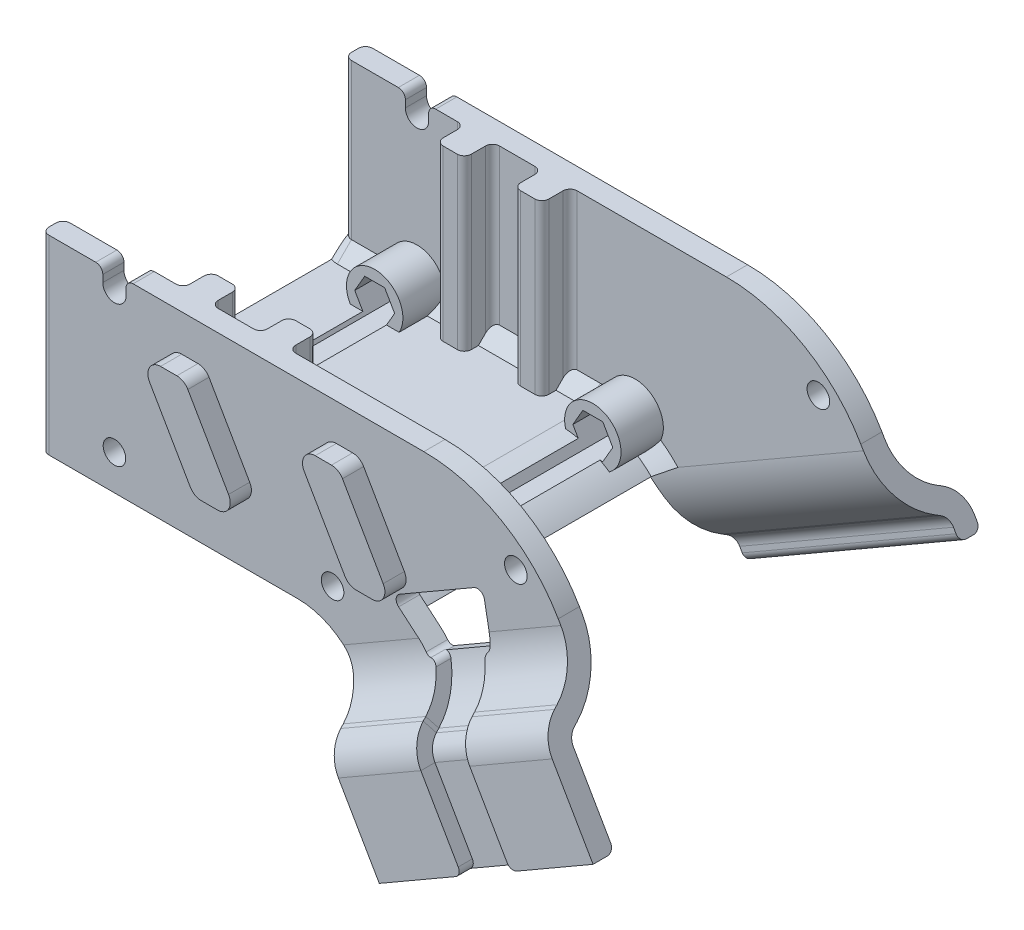
SolidWorks part; units mm, degrees
ref_plane "Front Plane" through (0, 0, 0) normal (0, 0, 1) x (1, 0, 0)
ref_plane "Top Plane" through (0, 0, 0) normal (0, 1, 0) x (1, 0, 0)
ref_plane "Right Plane" through (0, 0, 0) normal (1, 0, 0) x (0, 0, -1)
other "Configuration Table"
sketch "草图1" plane through (0, 145.9, 0) normal (0, 1, 0) x (1, 0, 0)
  line L14 (6.9526, -119.8723) -> (-44.7898, -119.8723) construction
  line L15 (-44.7898, -119.8723) -> (-47.2117, -119.8723) construction
  line L16 (6.9526, -73.9723) -> (-44.7898, -73.9723) construction
  line L17 (-47.2117, -73.9723) -> (-44.7898, -73.9723) construction
  line L18 (3.5151, -119.8723) -> (-44.7898, -119.8723)
  line L19 (-44.7898, -119.8723) -> (-47.2117, -119.8723)
  line L20 (3.5151, -73.9723) -> (-44.7898, -73.9723)
  line L21 (-47.2117, -73.9723) -> (-44.7898, -73.9723)
  line L22 (-47.2117, -73.9723) -> (-47.2117, -119.8723)
  line L23 (3.5151, -73.9723) -> (3.5151, -119.8723)
extrude "凸台-拉伸1" add sketch "草图1" against normal up to surface (30 mm away)
sketch "草图2" plane through (0, 0, 119.8723) normal (0, 0, 1) x (1, 0, 0)
  line L0 (3.5151, 145.9) -> (6.9526, 145.9)
  line L1 (-10.9453, 145.9) -> (-10.9453, 115.9)
  line L2 (-47.2117, 145.9) -> (3.5151, 145.9) construction
  line L3 (3.5151, 145.9) -> (-10.9453, 145.9)
  line L5 (28.9707, 132.7635) -> (-4.4253, 113.4822)
  line L6 (28.6032, 133.4) -> (28.9707, 132.7635)
  arc A0 (28.6032, 133.4) -> (6.9526, 145.9) centre (6.9526, 120.9) ccw construction
  arc A1 (28.6032, 133.4) -> (6.9526, 145.9) centre (6.9526, 120.9) ccw
  arc A2 (-4.4253, 113.4822) -> (-10.9453, 115.9) centre (-10.9453, 105.9) ccw construction
  arc A3 (-4.4253, 113.4822) -> (-10.9453, 115.9) centre (-10.9453, 105.9) ccw
extrude "凸台-拉伸5" add sketch "草图2" against normal up to surface (45.9 mm away) up to face at (-21.8483, 130.9, 73.9723)
sketch "草图4" plane through (0, 0, 119.8723) normal (0, 0, 1) x (1, 0, 0)
  line L0 (-4.4253, 113.4822) -> (6.9276, 120.0369)
  line L1 (3.5151, 118.0667) -> (28.9707, 132.7635) construction
  line L2 (6.9276, 120.0369) -> (8.6364, 117.0772)
  line L3 (8.6364, 117.0772) -> (-3.6007, 110.0121)
  line L4 (-3.6007, 110.0121) -> (-4.4253, 113.4822)
extrude "切除-拉伸1" cut sketch "草图4" against normal blind 72.5
shell "抽壳2" thickness 3
sketch "草图5" plane through (-50.2456, 87.0279, 0) normal (0.5, -0.866, 0) x (0.866, 0.5, 0)
  line L0 (91.4711, 73.9723) -> (91.4711, 119.8723) construction
  line L1 (52.9087, 119.8723) -> (91.4711, 119.8723)
  line L2 (52.9087, 119.8723) -> (52.9087, 116.8723)
  line L3 (52.9087, 116.8723) -> (91.4711, 116.8723)
  line L4 (91.4711, 119.8723) -> (91.4711, 116.8723)
  line L5 (56.0436, 116.8723) -> (88.4711, 116.8723) construction
sketch3d "3D草图1"
  line L0 (50.5425, 95.4, 126.8723) -> (34.7442, 122.7635, 126.8723) construction
  line L1 (50.5425, 95.4, 126.8723) -> (34.7442, 122.7635, 126.8723)
  line L2 (32.5792, 126.5135, 124.3723) -> (32.4348, 126.7635, 123.8723) construction
  line L5 (32.5792, 126.5135, 124.3723) -> (32.4348, 126.7635, 123.8723)
  arc A0 (32.5792, 126.5135, 124.3723) -> (34.7442, 122.7635, 126.8723) centre (34.7442, 122.7635, 121.8723) ccw construction
  arc A1 (28.9707, 132.7635, 119.8723) -> (32.4348, 126.7635, 123.8723) centre (28.9707, 132.7635, 127.8723) ccw construction
  arc A2 (32.5792, 126.5135, 124.3723) -> (34.7442, 122.7635, 126.8723) centre (34.7442, 122.7635, 121.8723) ccw
  arc A3 (28.9707, 132.7635, 119.8723) -> (32.4348, 126.7635, 123.8723) centre (28.9707, 132.7635, 127.8723) ccw
  point P5 (39.0743, 125.2635, 121.8723)
  point P8 (22.0425, 128.7635, 127.8723)
  point P9 (39.0743, 125.2635, 121.8723)
  point P10 (22.0425, 128.7635, 127.8723)
sweep "扫描2" add profiles "草图5" path "3D草图1"
ref_plane "基准面1" through (0, 0, 96.9223) normal (0, 0, -1) x (-1, 0, 0)
mirror "镜向1" about plane through (0, 0, 96.9223) normal (0, 0, -1) of "扫描2"
sketch "草图7" plane through (0, 0, 126.8723) normal (0, 0, 1) x (1, 0, 0)
  line L0 (40.5425, 112.7205) -> (7.1465, 93.4393)
  line L3 (7.1465, 93.4393) -> (17.1465, 76.1188)
  line L4 (17.1465, 76.1188) -> (50.5425, 95.4)
  line L5 (50.5425, 95.4) -> (40.5425, 112.7205)
  dimension "D1" = 20
extrude "切除-拉伸2" cut sketch "草图7" against normal blind 72.5
sketch "草图8" plane through (79.2163, 45.7356, 0) normal (0.866, 0.5, 0) x (0, 0, -1)
  line L0 (-66.9723, 88.9442) -> (-66.9723, 77.3476) construction
  line L1 (-69.9723, 93.563) -> (-69.4723, 93.2743) construction
  line L2 (-73.9723, 100.4912) -> (-73.9723, 101.2262) construction
  line L3 (-73.9723, 101.2262) -> (-119.8723, 101.2262) construction
  line L4 (-119.8723, 100.4912) -> (-119.8723, 101.2262) construction
  line L5 (-123.8723, 93.563) -> (-124.3723, 93.2743) construction
  line L6 (-126.8723, 88.9442) -> (-126.8723, 77.3476) construction
  line L7 (-66.9723, 88.9442) -> (-66.9723, 87.2262)
  line L8 (-69.9723, 93.563) -> (-69.4723, 93.2743)
  line L9 (-73.9723, 100.4912) -> (-73.9723, 101.2262)
  line L10 (-73.9723, 101.2262) -> (-119.8723, 101.2262)
  line L11 (-119.8723, 100.4912) -> (-119.8723, 101.2262)
  line L12 (-123.8723, 93.563) -> (-124.3723, 93.2743)
  line L13 (-126.8723, 88.9442) -> (-126.8723, 87.2262)
  line L15 (-126.8723, 87.2262) -> (-66.9723, 87.2262)
  arc A0 (-66.9723, 88.9442) -> (-69.4723, 93.2743) centre (-71.9723, 88.9442) ccw construction
  arc A1 (-73.9723, 100.4912) -> (-69.9723, 93.563) centre (-65.9723, 100.4912) ccw construction
  arc A2 (-123.8723, 93.563) -> (-119.8723, 100.4912) centre (-127.8723, 100.4912) ccw construction
  arc A3 (-124.3723, 93.2743) -> (-126.8723, 88.9442) centre (-121.8723, 88.9442) ccw construction
  arc A4 (-66.9723, 88.9442) -> (-69.4723, 93.2743) centre (-71.9723, 88.9442) ccw
  arc A5 (-73.9723, 100.4912) -> (-69.9723, 93.563) centre (-65.9723, 100.4912) ccw
  arc A6 (-123.8723, 93.563) -> (-119.8723, 100.4912) centre (-127.8723, 100.4912) ccw
  arc A7 (-124.3723, 93.2743) -> (-126.8723, 88.9442) centre (-121.8723, 88.9442) ccw
  dimension "D1" = 14
extrude "凸台-拉伸6" add sketch "草图8" against normal blind 3
sketch "草图9" plane through (0, 0, 66.9723) normal (0, 0, -1) x (-1, 0, 0)
  line L0 (-35.6032, 121.2756) -> (-2.2072, 101.9944)
  line L1 (-34.7442, 122.7635) -> (-40.5425, 112.7205) construction
  line L2 (-1.3482, 103.4822) -> (-7.1465, 93.4393) construction
  line L3 (-7.1465, 93.4393) -> (-40.5425, 112.7205) construction
  line L4 (-35.6032, 121.2756) -> (-40.5425, 112.7205)
  line L5 (-40.5425, 112.7205) -> (-7.1465, 93.4393)
  line L6 (-7.1465, 93.4393) -> (-2.2072, 101.9944)
extrude "切除-拉伸3" cut sketch "草图9" against normal blind 3
sketch "草图11" plane through (0, 0, 73.9723) normal (0, 0, -1) x (-1, 0, 0)
  line L0 (1.7732, 110.0135) -> (2.285, 110.9) construction
  line L1 (-1.8353, 103.7635) -> (1.6288, 109.7635) construction
  line L2 (-1.8353, 103.7635) -> (-17.6336, 76.4) construction
  line L3 (1.7732, 110.0135) -> (2.285, 110.9)
  line L4 (-1.8353, 103.7635) -> (1.6288, 109.7635)
  line L5 (-1.8353, 103.7635) -> (-17.6336, 76.4)
  line L7 (1.7732, 110.0135) -> (1.6288, 109.7635)
  line L8 (4.4253, 113.4822) -> (4.4253, 76.4)
  line L9 (4.4253, 76.4) -> (-17.6336, 76.4)
  arc A0 (10.9453, 115.9) -> (4.4253, 113.4822) centre (10.9453, 105.9) ccw construction
  arc A1 (4.4253, 113.4822) -> (2.285, 110.9) centre (10.9453, 105.9) ccw construction
  arc A2 (10.9453, 115.9) -> (4.4253, 113.4822) centre (10.9453, 105.9) ccw
  arc A3 (4.4253, 113.4822) -> (2.285, 110.9) centre (10.9453, 105.9) ccw
extrude "切除-拉伸4" cut sketch "草图11" against normal blind 68 and the other way blind 50 contours L8 A3 L3 L7 L4 L5 L9
sketch "草图12" plane through (0, 0, 73.9723) normal (0, 0, -1) x (-1, 0, 0)
  line L25 (19.2998, 124.1) -> (21.6092, 124.1)
  line L26 (23.1681, 125) -> (28.9416, 135)
  line L27 (27.3827, 137.7) -> (25.0733, 137.7)
  line L28 (23.5145, 136.8) -> (17.741, 126.8)
  line L29 (19.2998, 124.1) -> (21.6092, 124.1)
  line L30 (23.1681, 125) -> (28.9416, 135)
  line L31 (27.3827, 137.7) -> (25.0733, 137.7)
  line L32 (23.5145, 136.8) -> (17.741, 126.8)
  line L58 (-2.6284, 124.1) -> (-0.319, 124.1)
  line L59 (1.2399, 125) -> (7.0134, 135)
  line L60 (1.5863, 136.8) -> (-4.1872, 126.8)
  line L61 (5.4545, 137.7) -> (3.1451, 137.7)
  line L62 (-2.6284, 124.1) -> (-0.319, 124.1)
  line L63 (1.2399, 125) -> (7.0134, 135)
  line L64 (1.5863, 136.8) -> (-4.1872, 126.8)
  line L65 (5.4545, 137.7) -> (3.1451, 137.7)
  arc A20 (17.741, 126.8) -> (19.2998, 124.1) centre (19.2998, 125.9) ccw
  arc A21 (21.6092, 124.1) -> (23.1681, 125) centre (21.6092, 125.9) ccw
  arc A22 (28.9416, 135) -> (27.3827, 137.7) centre (27.3827, 135.9) ccw
  arc A23 (25.0733, 137.7) -> (23.5145, 136.8) centre (25.0733, 135.9) ccw
  arc A24 (17.741, 126.8) -> (19.2998, 124.1) centre (19.2998, 125.9) ccw
  arc A25 (21.6092, 124.1) -> (23.1681, 125) centre (21.6092, 125.9) ccw
  arc A26 (28.9416, 135) -> (27.3827, 137.7) centre (27.3827, 135.9) ccw
  arc A27 (25.0733, 137.7) -> (23.5145, 136.8) centre (25.0733, 135.9) ccw
  arc A47 (-4.1872, 126.8) -> (-2.6284, 124.1) centre (-2.6284, 125.9) ccw
  arc A48 (-0.319, 124.1) -> (1.2399, 125) centre (-0.319, 125.9) ccw
  arc A49 (7.0134, 135) -> (5.4545, 137.7) centre (5.4545, 135.9) ccw
  arc A50 (3.1451, 137.7) -> (1.5863, 136.8) centre (3.1451, 135.9) ccw
  arc A51 (-4.1872, 126.8) -> (-2.6284, 124.1) centre (-2.6284, 125.9) ccw
  arc A52 (-0.319, 124.1) -> (1.2399, 125) centre (-0.319, 125.9) ccw
  arc A53 (7.0134, 135) -> (5.4545, 137.7) centre (5.4545, 135.9) ccw
  arc A54 (3.1451, 137.7) -> (1.5863, 136.8) centre (3.1451, 135.9) ccw
  dimension "D1" = 0.2
  dimension "D2" = 0.2
extrude "凸台-拉伸7" add sketch "草图12" along normal blind 3
mirror "镜向2" about plane through (0, 0, 96.9223) normal (0, 0, -1) of "凸台-拉伸7"
sketch "草图13" plane through (0, 0, 119.8723) normal (0, 0, 1) x (1, 0, 0)
  circle A0 centre (19.9903, 134.9) radius 1.6
  circle A1 centre (-5.9904, 119.9) radius 1.6
  circle A2 centre (-36.9186, 120.9) radius 1.6
  circle A3 centre (-36.9186, 140.9) radius 1.65
  dimension "D1" = 3.2
  dimension "D2" = 3.2
  dimension "D3" = 3.2
  dimension "D4" = 3.3
extrude "切除-拉伸5" cut sketch "草图13" against normal blind 125
sketch "草图14" plane through (0, 0, 116.8723) normal (0, 0, -1) x (-1, 0, 0)
  line L1 (38.3331, 123.35) -> (35.5041, 123.35) construction
  line L2 (35.5041, 123.35) -> (34.0896, 120.9) construction
  line L3 (34.0896, 120.9) -> (35.5041, 118.45) construction
  line L4 (35.5041, 118.45) -> (38.3331, 118.45) construction
  line L5 (38.3331, 118.45) -> (39.7476, 120.9) construction
  line L6 (39.7476, 120.9) -> (38.3331, 123.35) construction
  circle A0 centre (36.9186, 120.9) radius 2.45 construction
  circle A1 centre (36.9186, 120.9) radius 4
  circle A2 centre (5.9904, 119.9) radius 4
  dimension "D2" = 8
  dimension "D3" = 8
  dimension "D1" = 4.9
extrude "凸台-拉伸8" add sketch "草图14" along normal blind 6
mirror "镜向3" about plane through (0, 0, 96.9223) normal (0, 0, -1) of "凸台-拉伸8"
sketch "草图16" plane through (0, 0, 116.8723) normal (0, 0, -1) x (-1, 0, 0)
  line L1 (35.5041, 123.35) -> (34.0896, 120.9)
  line L2 (34.0896, 120.9) -> (35.5041, 118.45)
  line L3 (35.5041, 118.45) -> (38.3331, 118.45)
  line L4 (38.3331, 118.45) -> (39.7476, 120.9)
  line L5 (39.7476, 120.9) -> (38.3331, 123.35)
  line L6 (38.3331, 123.35) -> (35.5041, 123.35)
  line L7 (4.5759, 122.35) -> (3.1614, 119.9)
  line L8 (3.1614, 119.9) -> (4.5759, 117.45)
  line L9 (4.5759, 117.45) -> (7.4049, 117.45)
  line L10 (7.4049, 117.45) -> (8.8194, 119.9)
  line L11 (8.8194, 119.9) -> (7.4049, 122.35)
  line L12 (7.4049, 122.35) -> (4.5759, 122.35)
  circle A0 centre (36.9186, 120.9) radius 2.45 construction
  circle A1 centre (5.9904, 119.9) radius 2.45 construction
  dimension "D1" = 4.9
  dimension "D2" = 4.9
extrude "切除-拉伸7" cut sketch "草图16" along normal up to surface (39.9 mm away)
sketch "草图17" plane through (0, 0, 119.8723) normal (0, 0, 1) x (1, 0, 0)
  line L32 (-47.2117, 159.0859) -> (-47.2117, 142.9)
  line L36 (29.8367, 125.2635) -> (29.9811, 125.0135)
  line L37 (29.9811, 125.0135) -> (32.1461, 121.2635)
  line L38 (26.0051, 131.9) -> (26.3726, 131.2635)
  line L39 (32.1461, 121.2635) -> (37.9444, 111.2205)
  line L40 (26.3726, 131.2635) -> (29.8367, 125.2635)
  line L41 (-47.2117, 142.9) -> (6.9526, 142.9)
  line L44 (26.0051, 131.9) -> (26.3726, 131.2635)
  line L47 (-47.2117, 142.9) -> (6.9526, 142.9)
  line L57 (-47.2117, 159.0859) -> (44.3687, 159.0859)
  line L59 (37.9444, 111.2205) -> (44.3687, 111.2205)
  line L60 (44.3687, 111.2205) -> (44.3687, 159.0859)
  line L61 (37.9444, 111.2205) -> (32.1461, 121.2635)
  line L62 (32.1461, 121.2635) -> (29.9811, 125.0135)
  line L63 (29.9811, 125.0135) -> (29.8367, 125.2635)
  line L64 (29.8367, 125.2635) -> (26.3726, 131.2635)
  line L65 (37.9444, 111.2205) -> (32.1461, 121.2635)
  line L66 (32.1461, 121.2635) -> (29.9811, 125.0135)
  line L67 (29.9811, 125.0135) -> (29.8367, 125.2635)
  line L68 (29.8367, 125.2635) -> (26.3726, 131.2635)
  arc A9 (26.0051, 131.9) -> (6.9526, 142.9) centre (6.9526, 120.9) ccw
  arc A10 (26.0051, 131.9) -> (6.9526, 142.9) centre (6.9526, 120.9) ccw
  dimension "D1" = 3
  dimension "D2" = 3
extrude "切除-拉伸8" cut sketch "草图17" against normal blind 83 and the other way blind 10
sketch "草图20" plane through (0, 142.9, 0) normal (0, 1, 0) x (1, 0, 0)
  line L0 (6.9526, -76.9723) -> (-47.2117, -76.9723) construction
  line L1 (-30.2117, -76.9723) -> (-26.2117, -76.9723)
  line L2 (-30.2117, -76.9723) -> (-30.2117, -80.9723)
  line L3 (-30.2117, -80.9723) -> (-26.2117, -80.9723)
  line L4 (-26.2117, -76.9723) -> (-26.2117, -80.9723)
  line L5 (-47.2117, -76.9723) -> (-47.2117, -73.9723) construction
  line L7 (-19.2117, -76.9723) -> (-15.2117, -76.9723)
  line L8 (-19.2117, -76.9723) -> (-19.2117, -80.9723)
  line L9 (-19.2117, -80.9723) -> (-15.2117, -80.9723)
  line L10 (-15.2117, -76.9723) -> (-15.2117, -80.9723)
  dimension "D1" = 4
  dimension "D2" = 4
  dimension "D3" = 17
  dimension "D4" = 4
  dimension "D5" = 4
  dimension "D6" = 7
extrude "凸台-拉伸9" add sketch "草图20" against normal up to surface (24 mm away) up to face at (-28.2747, 118.9, 96.9223)
mirror "镜向4" about plane through (0, 0, 96.9223) normal (0, 0, -1) of "凸台-拉伸9"
sketch "草图21" plane through (0, 0, 119.8723) normal (0, 0, 1) x (1, 0, 0)
  line L0 (-38.5686, 140.9) -> (-38.5686, 142.9)
  line L1 (6.9526, 142.9) -> (-47.2117, 142.9) construction
  line L2 (-38.5686, 142.9) -> (-35.2686, 142.9)
  line L3 (-35.2686, 142.9) -> (-35.2686, 140.9)
  arc A0 (-38.5686, 140.9) -> (-35.2686, 140.9) centre (-36.9186, 140.9) ccw
  circle A1 centre (-36.9186, 140.9) radius 1.65 construction
extrude "切除-拉伸11" cut sketch "草图21" against normal blind 87
ref_plane "基准面2" through (61.4628, 35.4856, 0) normal (0.866, 0.5, 0) x (0, 0, -1)
sketch "草图22" plane through (61.4628, 35.4856, 0) normal (0.866, 0.5, 0) x (0, 0, -1)
  line L0 (-126.8723, 77.3476) -> (-126.8723, 88.9442) construction
  line L1 (-126.8723, 77.3476) -> (-126.8723, 88.9442)
  line L2 (-119.8723, 100.4912) -> (-119.8723, 101.2262) construction
  line L3 (-124.3723, 93.2743) -> (-123.8723, 93.563) construction
  line L4 (-119.8723, 100.4912) -> (-119.8723, 101.2262)
  line L5 (-124.3723, 93.2743) -> (-123.8723, 93.563)
  arc A0 (-123.8723, 93.563) -> (-119.8723, 100.4912) centre (-127.8723, 100.4912) ccw construction
  arc A1 (-124.3723, 93.2743) -> (-126.8723, 88.9442) centre (-121.8723, 88.9442) ccw construction
  arc A2 (-123.8723, 93.563) -> (-119.8723, 100.4912) centre (-127.8723, 100.4912) ccw
  arc A3 (-124.3723, 93.2743) -> (-126.8723, 88.9442) centre (-121.8723, 88.9442) ccw
sketch "草图23" plane through (-38.6738, 66.985, 0) normal (0.5, -0.866, 0) x (0.866, 0.5, 0)
  line L0 (70.9711, 126.8723) -> (70.9711, 123.8723) construction
  line L1 (88.4711, 126.8723) -> (53.4711, 126.8723) construction
  line L2 (53.4711, 123.8723) -> (88.4711, 123.8723) construction
  line L4 (66.9711, 128.8723) -> (74.9711, 128.8723)
  line L5 (66.9711, 128.8723) -> (66.9711, 124.8723)
  line L6 (66.9711, 124.8723) -> (74.9711, 124.8723)
  line L7 (74.9711, 128.8723) -> (74.9711, 124.8723)
  line L8 (66.9711, 128.8723) -> (74.9711, 124.8723) construction
  line L9 (66.9711, 124.8723) -> (74.9711, 128.8723) construction
  point P6 (70.9711, 126.8723)
  dimension "D1" = 2
  dimension "D2" = 8
  dimension "D3" = 4
sweep "切除-扫描1" cut profiles "草图23" path "草图22"
sketch "草图24" plane through (0, 0, 119.8723) normal (0, 0, 1) x (1, 0, 0)
  line L0 (22.789, 102.4705) -> (6.2244, 131.1612) construction
  line L1 (26.2531, 104.4705) -> (19.3249, 100.4705) construction
  line L2 (2.2938, 122.9692) -> (15.2842, 130.4692)
  line L3 (37.9444, 111.2205) -> (26.2531, 104.4705) construction
  line L4 (7.9589, 118.157) -> (16.6191, 123.157)
  line L5 (2.2938, 122.9692) -> (7.9589, 118.157)
  line L6 (15.2842, 130.4692) -> (16.6191, 123.157)
  point P8 (12.289, 120.657)
  point P9 (8.789, 126.7192)
  dimension "D1" = 7
  dimension "D2" = 21
  dimension "D3" = 15
  dimension "D4" = 10
extrude "切除-拉伸12" cut sketch "草图24" against normal blind 26 and the other way blind 26
fillet "圆角1" radius 1 4 edges at (16.6191, 123.157, 118.6241) (15.2842, 130.4692, 118.3723) (2.2938, 122.9692, 118.3723) (7.9589, 118.157, 118.6241)
fillet "圆角2" radius 1 4 edges at (26.2531, 104.4705, 125.8723) (19.3249, 100.4705, 125.8723) (15.7531, 122.657, 119.1348) (8.8249, 118.657, 119.1348)
fillet "圆角3" radius 1 6 edges at (22.789, 102.4705, 123.8723) (17.8497, 111.0256, 66.9723) (17.8497, 111.0256, 69.9723) (-47.2117, 129.4, 73.9723) (-47.2117, 130.9, 116.8723) (-47.2117, 129.4, 119.8723)
chamfer "倒角1" distance 2 angle 45 14 edges at (-31.8331, 118.9, 116.8723) (-2.6398, 115.9009, 116.8723) (-43.2972, 118.9, 76.9723) (-2.6398, 115.9009, 76.9723) (-31.8331, 118.9, 76.9723) (-22.7117, 118.9, 76.9723) (-22.7117, 118.9, 116.8723) (-13.0785, 118.9, 116.8723) (-10.3977, 118.8885, 116.8723) (-13.0785, 118.9, 76.9723) (-10.3977, 118.8885, 76.9723) (-43.2972, 118.9, 116.8723) (-46.9188, 118.9, 76.6794) (-46.9188, 118.9, 117.1652)
fillet "圆角4" radius 1 20 edges at (-15.2117, 131.9, 116.8723) (-15.2117, 131.9, 76.9723) (-26.2117, 131.9, 76.9723) (-19.2117, 131.9, 76.9723) (-30.2117, 131.9, 76.9723) (-26.2117, 130.9, 80.9723) (-30.2117, 130.9, 80.9723) (-15.2117, 130.9, 80.9723) (-19.2117, 130.9, 80.9723) (-30.2117, 130.9, 112.8723) (-26.2117, 130.9, 112.8723) (-19.2117, 130.9, 112.8723) (-15.2117, 130.9, 112.8723) (-35.2686, 142.9, 118.3723) (-38.5686, 142.9, 118.3723) (-38.5686, 142.9, 75.4723) (-35.2686, 142.9, 75.4723) (-30.2117, 131.9, 116.8723) (-19.2117, 131.9, 116.8723) (-26.2117, 131.9, 116.8723)
